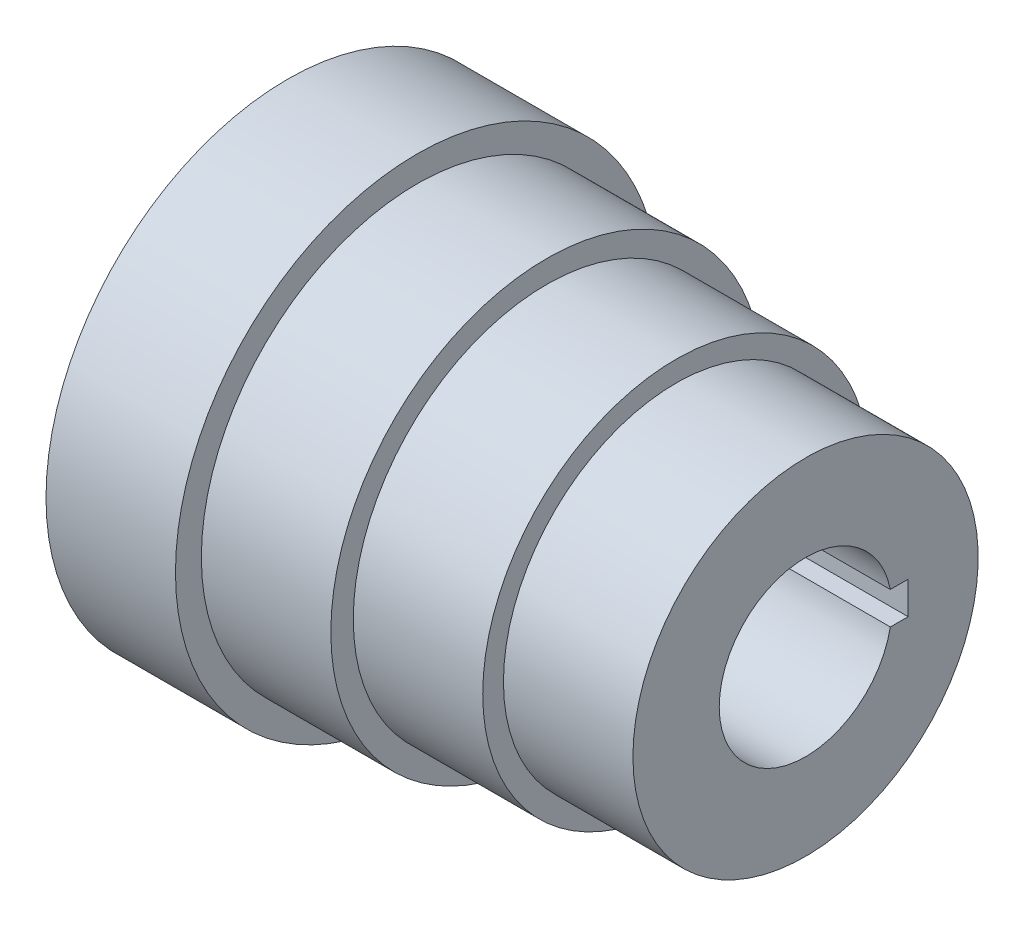
SolidWorks part; units mm, degrees
ref_plane "Front Plane" through (0, 0, 0) normal (0, 0, 1) x (1, 0, 0)
ref_plane "Top Plane" through (0, 0, 0) normal (0, 1, 0) x (1, 0, 0)
ref_plane "Right Plane" through (0, 0, 0) normal (1, 0, 0) x (0, 0, -1)
sketch "Sketch1" plane through (0, 0, 0) normal (0, 0, 1) x (1, 0, 0)
  line L0 (-38.1, 0) -> (38.1, 0) construction
  line L1 (-38.1, 35.56) -> (-19.05, 35.56)
  line L2 (-19.05, 35.56) -> (-19.05, 31.75)
  line L3 (-19.05, 31.75) -> (0, 31.75)
  line L4 (0, 31.75) -> (0, 28.448)
  line L5 (0, 28.448) -> (19.05, 28.448)
  line L6 (19.05, 28.448) -> (19.05, 25.4)
  line L7 (19.05, 25.4) -> (38.1, 25.4)
  line L8 (38.1, 25.4) -> (38.1, 12.7)
  line L9 (38.1, 12.7) -> (-6.6124, 12.7)
  line L10 (-6.6124, 12.7) -> (-6.6124, 25.4) construction
  line L11 (-19.0964, 25.4) -> (-38.1, 25.4)
  line L12 (-38.1, 25.4) -> (-38.1, 35.56)
  line L13 (-19.05, 25.3973) -> (-19.0964, 25.4)
  arc A0 (-19.05, 25.3973) -> (-6.6124, 12.7) centre (-19.3124, 12.7) cw
  point P17 (0, 0)
  point P18 (0, 0)
  point P19 (0, 0)
  point P21 (0, 0)
  point P22 (0, 0)
  dimension "D13" = 19.05
  dimension "D14" = 19.05
  dimension "D2" = 12.7
  dimension "D3" = 19.05
  dimension "D4" = 19.05
  dimension "D5" = 19.05
  dimension "D6" = 25.4
  dimension "D7" = 71.12
  dimension "D8" = 19.05
  dimension "D9" = 63.5
  dimension "D10" = 56.896
  dimension "D11" = 50.8
  dimension "D12" = 50.8
revolve "Revolve1" add sketch "Sketch1" angle 360 about L0
sketch "Sketch3" plane through (38.1, 0, 0) normal (1, 0, 0) x (0, 0, -1)
  line L0 (0, 0) -> (12.7, 0) construction
  line L2 (10.3124, -2.3876) -> (15.0876, -2.3876)
  line L3 (10.3124, -2.3876) -> (10.3124, 2.3876)
  line L4 (10.3124, 2.3876) -> (15.0876, 2.3876)
  line L5 (15.0876, -2.3876) -> (15.0876, 2.3876)
  line L6 (10.3124, -2.3876) -> (15.0876, 2.3876) construction
  line L7 (10.3124, 2.3876) -> (15.0876, -2.3876) construction
  circle A0 centre (0, 0) radius 12.7 construction
  point P10 (0, 0)
  dimension "D1" = 4.7752
  dimension "D2" = 2.3876
extrude "Cut-Extrude1" cut sketch "Sketch3" against normal through all
